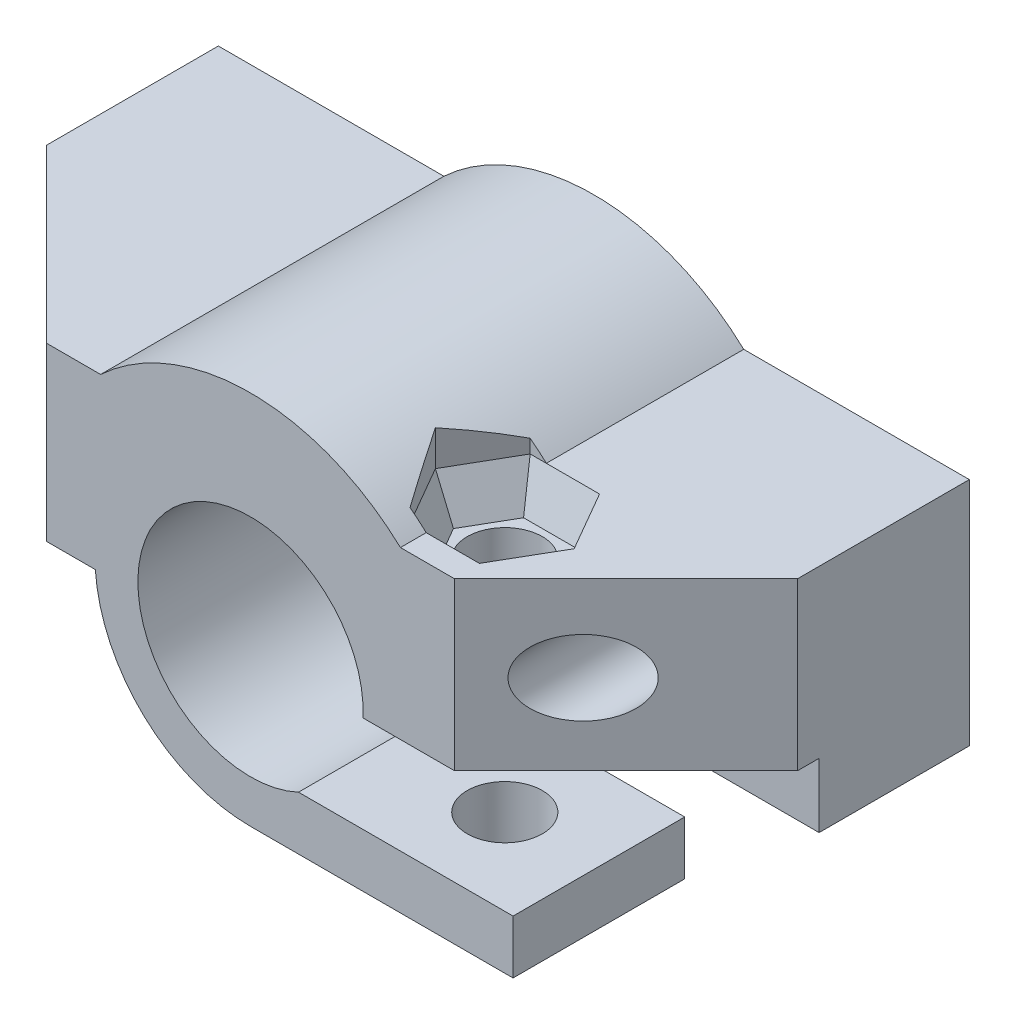
SolidWorks part; units mm, degrees
ref_plane "Plano frontal" through (0, 0, 0) normal (0, 0, 1) x (1, 0, 0)
ref_plane "Plano superior" through (0, 0, 0) normal (0, 1, 0) x (1, 0, 0)
ref_plane "Plano direito" through (0, 0, 0) normal (1, 0, 0) x (0, 0, -1)
sketch "Esboço1" plane through (0, 0, 0) normal (0, 0, 1) x (1, 0, 0)
  line L0 (17.5, 7.5) -> (6.9866, 7.5)
  line L1 (15.8072, -0.25) -> (12.7361, -0.25)
  line L2 (0, 0) -> (0, 8.1134) construction
  line L3 (-17.5, 7.5) -> (-6.9866, 7.5)
  line L4 (-17.5, -0.5) -> (-7.2327, -0.5)
  line L5 (0, -7.25) -> (12.2361, -7.25)
  line L6 (12.2361, -7.25) -> (12.2361, -4.75)
  line L7 (12.2361, -4.75) -> (2.2361, -4.75)
  line L8 (-17.5, 7.5) -> (-17.5, -0.5)
  line L15 (17.5, 7.5) -> (17.5, -0.25)
  line L16 (17.5, -0.25) -> (15.8072, -0.25)
  line L23 (5.244, -0.25) -> (12.7361, -0.25)
  arc A0 (6.9866, 7.5) -> (-6.9866, 7.5) centre (0, 0) ccw
  arc A1 (5.244, -0.25) -> (2.2361, -4.75) centre (0, 0) ccw
  circle A3 centre (12.5, 3.5) radius 1.75
  circle A4 centre (-12.5, 3.5) radius 1.75
  arc A6 (-7.2327, -0.5) -> (0, -7.25) centre (0, 0) ccw
  point P1 (-17.5, 3.5)
  point P3 (17.8193, 9.9747)
  point P7 (16.7306, 7.881)
  point P14 (12.7361, -2.25)
  point P17 (12.7361, -2.5383)
  dimension "D2" = 10.5
  dimension "D3" = 5
  dimension "D4" = 4
  dimension "D5" = 3.5
  dimension "D7" = 2
  dimension "D1" = 25
  dimension "D6" = 2.5
  dimension "D8" = 3.5
  dimension "D9" = 4.5
  dimension "D10" = 5
  dimension "D14" = 10
extrude "Ressalto-extrusão1" add sketch "Esboço1" along normal blind 16
sketch "Esboço3" plane through (0, -7.25, 0) normal (0, -1, 0) x (1, 0, 0)
  line L0 (5.5, 0) -> (5.5, 16) construction
  line L1 (0, 0) -> (12.2361, 0) construction
  line L2 (0, 16) -> (12.2361, 16) construction
  line L3 (0, 16) -> (0, 0) construction
  circle A0 centre (7.85, 12) radius 1.75
  point P8 (0, 8)
  point P11 (5.5, 8)
  point P12 (5.5, 8)
  point P13 (7.85, 11.5926)
  dimension "D2" = 0.6
  dimension "D3" = 3.5
  dimension "D1" = 5.5
  dimension "D4" = 4
extrude "Corte-extrusão2" cut sketch "Esboço3" against normal through all
sketch "Esboço4" plane through (0, 7.5, 0) normal (0, 1, 0) x (1, 0, 0)
  line L1 (11.0832, -12) -> (9.4666, -9.2)
  line L2 (9.4666, -9.2) -> (6.2334, -9.2)
  line L3 (6.2334, -9.2) -> (4.6168, -12)
  line L4 (4.6168, -12) -> (6.2334, -14.8)
  line L5 (6.2334, -14.8) -> (9.4666, -14.8)
  line L6 (9.4666, -14.8) -> (11.0832, -12)
  circle A0 centre (7.85, -12) radius 2.8 construction
  circle A1 centre (7.85, -12) radius 1.75 construction
  dimension "D1" = 5.6
extrude "Corte-extrusão3" cut sketch "Esboço4" against normal blind 2 draft 20 and the other way blind 6
sketch "Esboço5" plane through (0, -7.25, 0) normal (0, -1, 0) x (1, 0, 0)
  line L0 (0, 16) -> (12.2361, 16) construction
  line L1 (12.2361, 0) -> (-17.6435, 0)
  line L2 (12.2361, 0) -> (12.2361, 8)
  line L3 (12.2361, 8) -> (-17.6435, 8)
  line L4 (-17.6435, 0) -> (-17.6435, 8)
  point P7 (-17.6435, 0)
  dimension "D1" = 8
extrude "Corte-extrusão4" cut sketch "Esboço5" against normal up to surface (6.75 mm away) up to face at (-12.3664, -0.5, 8)
sketch "Esboço6" plane through (0, -0.25, 0) normal (0, -1, 0) x (1, 0, 0)
  line L1 (6.5, 7) -> (17.5, 7)
  line L2 (6.5, 7) -> (6.5, 0)
  line L3 (6.5, 0) -> (17.5, 0)
  line L4 (17.5, 7) -> (17.5, 0)
  line L5 (5.244, 0) -> (17.5, 0) construction
  line L7 (5.244, 0) -> (17.5, 0) construction
  line L10 (-6.5, 0) -> (-17.5, 0)
  line L11 (-6.5, 0) -> (-6.5, 7)
  line L12 (-6.5, 7) -> (-17.5, 7)
  line L13 (-17.5, 0) -> (-17.5, 7)
  line L14 (0, 0) -> (0, 8.8913) construction
  point P4 (-6.5, 0)
  point P5 (0, 0)
  dimension "D1" = 13
  dimension "D2" = 7
extrude "Ressalto-extrusão2" add sketch "Esboço6" along normal blind 3
sketch "Esboço7" plane through (0, 0, 0) normal (0, 0, -1) x (-1, 0, 0)
  line L0 (0, 0) -> (0, 7.5493) construction
  line L1 (-15.3, -0.45) -> (-9.7, -0.45)
  line L2 (-15.3, -0.45) -> (-15.3, 2.05)
  line L3 (-15.3, 2.05) -> (-9.7, 2.05)
  line L4 (-9.7, -0.45) -> (-9.7, 2.05)
  line L5 (-15.3, -0.45) -> (-9.7, 2.05) construction
  line L6 (-15.3, 2.05) -> (-9.7, -0.45) construction
  line L7 (15.3, 2.05) -> (9.7, -0.45) construction
  line L8 (15.3, -0.45) -> (9.7, 2.05) construction
  line L9 (9.7, -0.45) -> (9.7, 2.05)
  line L10 (15.3, 2.05) -> (9.7, 2.05)
  line L11 (15.3, -0.45) -> (15.3, 2.05)
  line L12 (15.3, -0.45) -> (9.7, -0.45)
  circle A1 centre (-12.5, 3.5) radius 1.75 construction
  point P0 (-12.5, 0.8)
  point P9 (-12.5, 3.5)
  point P17 (12.5, 3.5)
  point P18 (12.5, 0.8)
  dimension "D1" = 5.6
  dimension "D2" = 2.5
  dimension "D3" = 0.3
extrude "Corte-extrusão6" cut sketch "Esboço7" against normal blind 8
sketch "Esboço8" plane through (0, -3.25, 0) normal (0, -1, 0) x (1, 0, 0)
  line L0 (15.3, 0) -> (9.7, 0) construction
  line L1 (15.3, 0) -> (9.7, 0) construction
  line L2 (0, 0) -> (0, 5.9509) construction
  line L3 (-15.3, 0) -> (-9.7, 0) construction
  circle A0 centre (12.5, 4) radius 1.65
  circle A1 centre (-12.5, 4) radius 1.65
  point P5 (12.5, 0)
  point P12 (-12.5, 0)
  dimension "D2" = 3.3
  dimension "D1" = 4
extrude "Corte-extrusão7" cut sketch "Esboço8" against normal blind 6
chamfer "Chanfro1" distance 8 angle 45 2 edges at (17.5, 3.625, 16) (-17.5, 3.5, 16)
